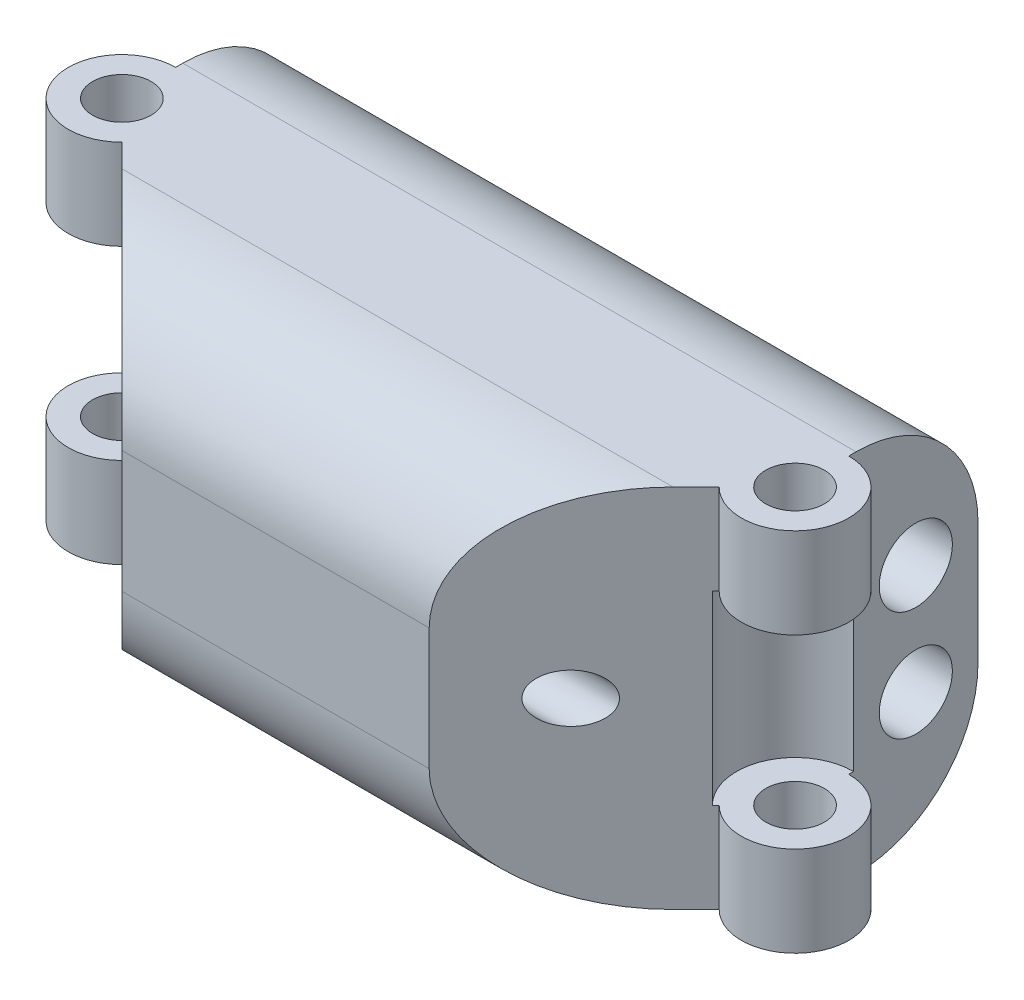
SolidWorks part; units mm, degrees
ref_plane "Front Plane" through (0, 0, 0) normal (1, 0, 0) x (0, 1, 0)
ref_plane "Top Plane" through (0, 0, 0) normal (0, 0, 1) x (0, 1, 0)
ref_plane "Right Plane" through (0, 0, 0) normal (0, 1, 0) x (-1, 0, 0)
sketch "Sketch1" plane through (0, 0, 0) normal (0, 1, 0) x (-1, 0, 0)
  line L1 (-6.3, 7.5) -> (6.3, 7.5)
  line L4 (13.8, -7.5) -> (-13.8, -7.5)
  line L6 (-13.8, -7.5) -> (-13.8, 0)
  line L7 (-13.8, 7.5) -> (-6.3, 7.5) construction
  line L8 (6.3, 7.5) -> (13.8, 7.5) construction
  line L9 (6.3, 7.5) -> (13.8, 0)
  line L10 (-13.8, 7.5) -> (13.8, -7.5) construction
  line L11 (-13.8, 0) -> (-6.3, 7.5)
  line L12 (-13.8, 7.5) -> (-13.8, 0) construction
  line L13 (13.8, 0) -> (13.8, -7.5)
  line L14 (13.8, 0) -> (13.8, 7.5) construction
  arc A4 (12.1029, 1.6971) -> (13.8, -2.4) centre (13.8, 0) ccw
  circle A5 centre (13.8, 0) radius 1.2 construction
  circle A6 centre (13.8, 0) radius 2.2 construction
  arc A7 (-13.8, -2.4) -> (-12.1029, 1.6971) centre (-13.8, 0) ccw
  dimension "D3" = 1
  dimension "D4" = 0.2
  dimension "D5" = 4.8
  dimension "D2" = 2.4
  dimension "D1" = 15
extrude "Boss-Extrude1" add sketch "Sketch1" along normal blind 7.5 and the other way blind 7.5 contours L1 L4 region at (0, 0, -0.7982)
sketch "Sketch5" plane through (13.8, 0, 0) normal (1, 0, 0) x (0, 1, 0)
  line L0 (0, -2.4) -> (0, -7.5) construction
  line L1 (-2.25, -4.95) -> (2.25, -4.95) construction
  line L2 (-7.5, -2.4) -> (7.5, -2.4) construction
  line L3 (-7.5, -7.5) -> (7.5, -7.5) construction
  circle A0 centre (-2.25, -4.95) radius 1.5
  circle A1 centre (2.25, -4.95) radius 1.5
  point P4 (0.75, -4.95)
  point P7 (0, -4.95)
  point P8 (-0.75, -4.95)
  point P9 (0, -4.95)
  dimension "D1" = 3
  dimension "D2" = 1.5
  dimension "D3" = 0
extrude "Cut-Extrude3" cut sketch "Sketch5" against normal up to next
fillet "Fillet1" radius 5 2 edges at (0, -7.5, -7.5) (0, 7.5, -7.5)
sketch "Sketch3" plane through (0, 0, 0) normal (1, 0, 0) x (0, 1, 0)
  line L0 (-7.5, 4.5985) -> (7.5, 4.5985) construction
  line L3 (-7.5, 1.6971) -> (-7.5, 7.5) construction
  line L4 (7.5, 1.6971) -> (7.5, 7.5) construction
  circle A0 centre (0, 4.5985) radius 1
  dimension "D1" = 2
extrude "Cut-Extrude2" cut sketch "Sketch3" against normal up to next and the other way up to next
fillet "Fillet2" radius 5 2 edges at (0, 7.5, 7.5) (0, -7.5, 7.5)
sketch "Sketch6" plane through (0, 0, 0) normal (0, 1, 0) x (-1, 0, 0)
  line L4 (0, 7.5) -> (0, -7.5) construction
  line L5 (-6.3, 7.5) -> (6.3, 7.5) construction
  line L6 (13.8, -7.5) -> (-13.8, -7.5) construction
  line L7 (-12.1029, 1.6971) -> (-12.2444, 1.5556)
  line L9 (-13.8, -2.4) -> (-13.8, -2.2)
  line L10 (-12.1029, 1.6971) -> (-11.3, 2.5) construction
  line L11 (13.8, -2.4) -> (13.8, -2.2)
  line L12 (12.1029, 1.6971) -> (12.2444, 1.5556)
  arc A6 (-12.2444, 1.5556) -> (-13.8, -2.2) centre (-13.8, 0) ccw
  circle A7 centre (-13.8, 0) radius 1.2
  arc A8 (-13.8, -2.4) -> (-12.1029, 1.6971) centre (-13.8, 0) ccw
  arc A9 (-13.8, -2.4) -> (-12.1029, 1.6971) centre (-13.8, 0) ccw construction
  arc A10 (13.8, -2.4) -> (12.1029, 1.6971) centre (13.8, 0) cw
  circle A11 centre (13.8, 0) radius 1.2
  arc A12 (12.2444, 1.5556) -> (13.8, -2.2) centre (13.8, 0) cw
  dimension "D1" = 0.2
  dimension "D2" = 1
extrude "Boss-Extrude2" add sketch "Sketch6" along normal blind 3.7 from offset 3.8
extrude "Boss-Extrude3" add sketch "Sketch6<4>" against normal blind 3.7 from offset 3.8 offset against normal yes
sketch "Sketch6<4>" plane through (0, 0, 0) normal (0, 1, 0) x (-1, 0, 0) same geometry as "Sketch6"
